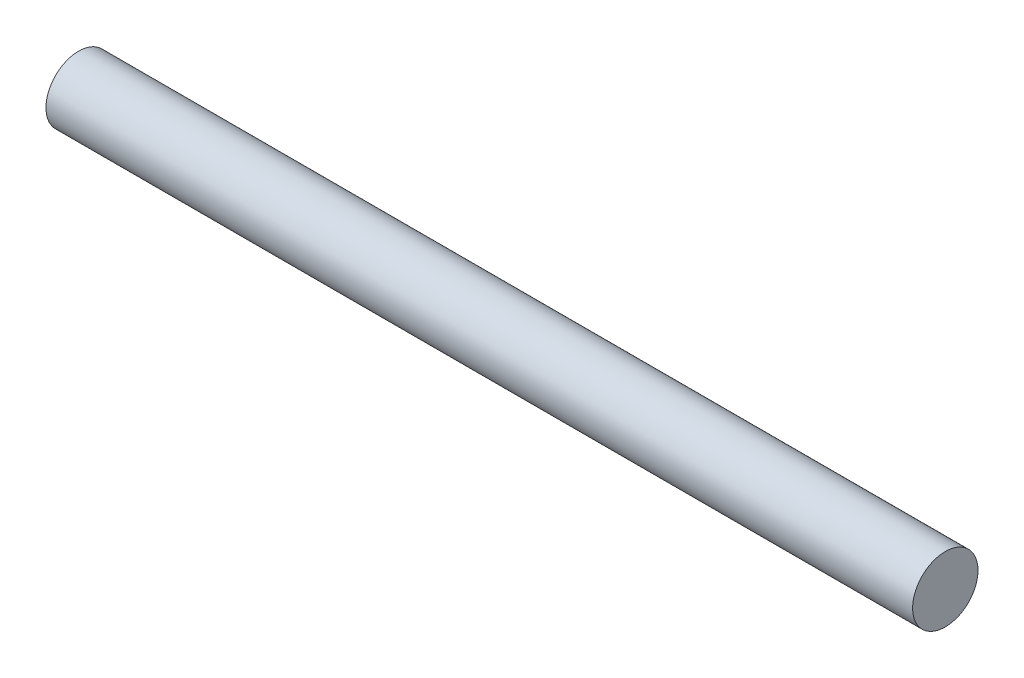
SolidWorks part; units mm, degrees
ref_plane "前视基准面" through (0, 0, 0) normal (0, 0, 1) x (1, 0, 0)
ref_plane "上视基准面" through (0, 0, 0) normal (0, 1, 0) x (1, 0, 0)
ref_plane "右视基准面" through (0, 0, 0) normal (1, 0, 0) x (0, 0, -1)
sketch "草图1" plane through (0, 0, 0) normal (1, 0, 0) x (0, 0, -1)
  circle A0 centre (0, 0) radius 4
  dimension "D1" = 8
extrude "凸台-拉伸1" add sketch "草图1" along normal blind 150
sketch "草图4" plane through (0, 0, 0) normal (-1, 0, 0) x (0, 0, 1)
  circle A1 centre (0, 0) radius 4
  circle A2 centre (0, 0) radius 4
  dimension "D1" = 0
extrude "切除-拉伸1" cut sketch "草图4" against normal up to surface (44 mm away)
